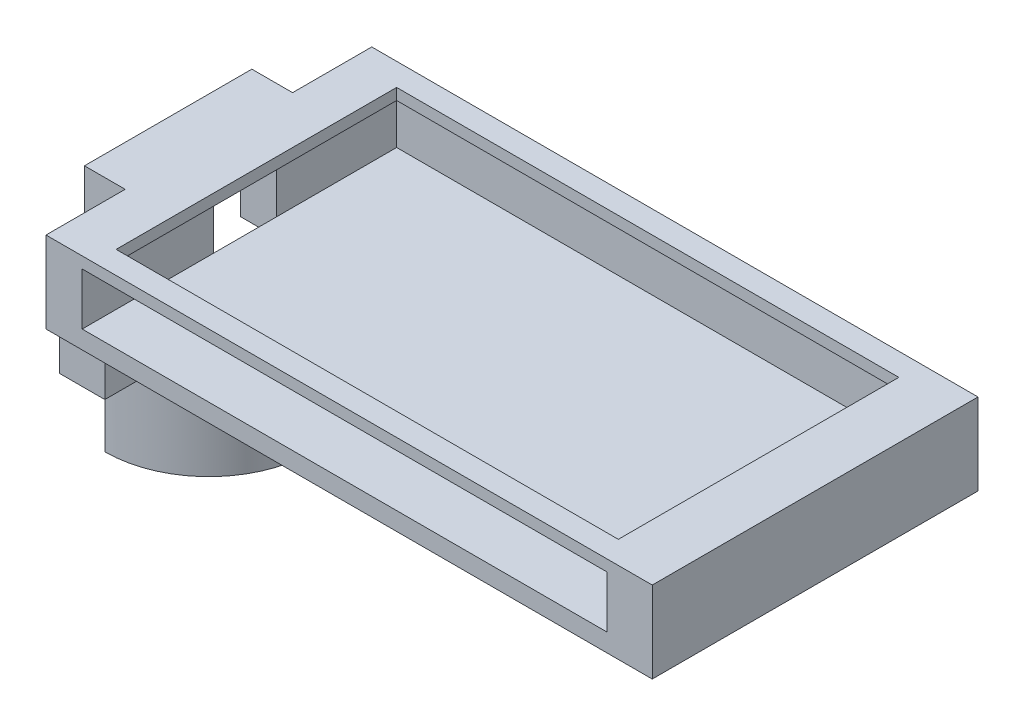
SolidWorks part; units mm, degrees
ref_plane "Front Plane" through (0, 0, 0) normal (0, 0, 1) x (1, 0, 0)
ref_plane "Top Plane" through (0, 0, 0) normal (0, 1, 0) x (1, 0, 0)
ref_plane "Right Plane" through (0, 0, 0) normal (1, 0, 0) x (0, 0, -1)
sketch "Sketch5" plane through (0, 0, 0) normal (0, 1, 0) x (1, 0, 0)
  line L0 (-124, 0) -> (-134, 0)
  line L1 (0, 0) -> (-1.9533, 0)
  line L2 (0, 0) -> (0, 72)
  line L3 (0, 72) -> (-134, 72)
  line L4 (-134, 0) -> (-134, 72)
  line L6 (-10, 2.5) -> (-10, 69.5)
  line L7 (-10, 69.5) -> (-126, 69.5)
  line L8 (-126, 2.5) -> (-126, 69.5)
  line L9 (-126, 2.5) -> (-10, 2.5)
  line L10 (-124, 0) -> (-1.9533, 0)
  dimension "D1" = 72
  dimension "D2" = 134
  dimension "D3" = 116
  dimension "D5" = 10
  dimension "D6" = 2.5
  dimension "D7" = 2.5
extrude "Main Body" add sketch "Sketch5" against normal blind 14 contours L1 L8 L7 L6 L2 L3 L4 region at (-129, 0, -1.5212)
sketch "Sketch6" plane through (0, 0, 0) normal (0, 1, 0) x (1, 0, 0)
  line L5 (-10, 2.5) -> (-126, 2.5)
  line L6 (-10, 2.5) -> (-10, 69.5)
  line L7 (-10, 69.5) -> (-126, 69.5)
  line L8 (-126, 2.5) -> (-126, 69.5)
  line L9 (-12.5, 5) -> (-123.5, 5)
  line L10 (-12.5, 5) -> (-12.5, 67)
  line L11 (-12.5, 67) -> (-123.5, 67)
  line L12 (-123.5, 5) -> (-123.5, 67)
  dimension "D1" = 2.5
  dimension "D2" = 2.5
  dimension "D3" = 2.5
  dimension "D4" = 2.5
extrude "Rail" add sketch "Sketch6" against normal blind 2.5
sketch "Sketch8" plane through (0, 0, 0) normal (0, 0, 1) x (1, 0, 0)
  line L0 (-134, -14) -> (-134, 0) construction
  line L1 (0, -14) -> (-134, -14)
  line L2 (0, -14) -> (0, -18)
  line L3 (0, -18) -> (-134, -18)
  line L4 (-134, -14) -> (-134, -18)
  dimension "D1" = 4
extrude "Cover" add sketch "Sketch8" against normal up to surface (72 mm away) up to face at (-67, -7, -72)
sketch "Sketch9" plane through (-134, 0, 0) normal (-1, 0, 0) x (0, 0, 1)
  line L0 (-72, -18) -> (0, -18) construction
  line L1 (-29, -18) -> (-43, -18)
  line L2 (-29, -18) -> (-29, -4)
  line L3 (-29, -4) -> (-43, -4)
  line L4 (-43, -18) -> (-43, -4)
  line L5 (-72, -18) -> (-72, 0) construction
  dimension "D1" = 14
  dimension "D2" = 14
  dimension "D3" = 29
extrude "SiPM Window" cut sketch "Sketch9" against normal up to surface (8 mm away) up to face at (-126, -8.25, -36)
sketch "Sketch10" plane through (0, -18, 0) normal (0, -1, 0) x (1, 0, 0)
  line L0 (-134, -72) -> (-134, -43) construction
  line L4 (-134, -29) -> (-134, 0) construction
  line L5 (-134, -72) -> (0, -72) construction
  line L6 (-134, -16) -> (-134, -13)
  line L7 (-134, -56) -> (-134, -59)
  arc A0 (-134, -56) -> (-134, -16) centre (-134, -36) ccw
  arc A1 (-134, -59) -> (-134, -13) centre (-134, -36) ccw
  line M4 (-134, -43) -> (-134, -72)
  line M8 (-134, 0) -> (-134, -29)
  dimension "D2" = 20
  dimension "D1" = 36
  dimension "D3" = 3
  dimension "D4" = 3
extrude "Tube Adapter" add sketch "Sketch10" along normal blind 30 contours A1 A0 M4 M8 region at (-133.4857, -18, -14.5)
sketch "Sketch11" plane through (0, -18, 0) normal (0, -1, 0) x (1, 0, 0)
  line L0 (-134, -59) -> (-134, -69)
  line L5 (-134, -72) -> (-134, -59) construction
  line L6 (-134, -69) -> (-124, -69)
  line L7 (-124, -69) -> (-124, -56.7123)
  arc A0 (-134, -59) -> (-124, -56.7123) centre (-134, -36) ccw
  dimension "D1" = 10
  dimension "D2" = 10
extrude "Right Screw Terminal" add sketch "Sketch11" along normal blind 10
sketch "Sketch12" plane through (-134, 0, 0) normal (-1, 0, 0) x (0, 0, 1)
  line L2 (-69, -28) -> (-69, -18) construction
  line L3 (-59, -28) -> (-69, -28) construction
  circle A0 centre (-64, -23) radius 1.524
  dimension "D3" = 5
  dimension "D1" = 3.048
  dimension "D2" = 5
extrude "Right Screw Hole" cut sketch "Sketch12" against normal up to next
sketch "Sketch13" plane through (0, -18, 0) normal (0, -1, 0) x (-1, 0, 0)
  line L2 (134, 13) -> (134, 3)
  line L3 (134, 3) -> (124, 3)
  line L4 (124, 15.2877) -> (124, 3)
  arc A0 (134, 13) -> (124, 15.2877) centre (134, 36) cw
  dimension "D1" = 10
  dimension "D2" = 10
extrude "Left Screw Terminal" add sketch "Sketch13" along normal blind 10
sketch "Sketch14" plane through (-134, 0, 0) normal (-1, 0, 0) x (0, 0, 1)
  line L0 (-3, -28) -> (-3, -18) construction
  line L1 (-3, -28) -> (-13, -28) construction
  circle A0 centre (-8, -23) radius 1.524
  dimension "D3" = 3.048
  dimension "D1" = 5
  dimension "D2" = 5
extrude "Left Screw Hole" cut sketch "Sketch14" against normal up to next
sketch "Sketch15" plane through (-134, 0, 0) normal (-1, 0, 0) x (0, 0, 1)
  line L0 (-29, -18) -> (-16, -18) construction
  line L1 (-17.5, -18) -> (-54.5, -18)
  line L2 (-17.5, -18) -> (-17.5, 0)
  line L3 (-17.5, 0) -> (-54.5, 0)
  line L4 (-54.5, -18) -> (-54.5, 0)
  line L7 (0, 0) -> (-72, 0) construction
  line L8 (-43, -4) -> (-43, -18) construction
  dimension "D1" = 37
  dimension "D2" = 11.5
extrude "SiPM Mount" add sketch "Sketch15" along normal blind 9
sketch "Sketch17" plane through (0, -18, 0) normal (0, -1, 0) x (1, 0, 0)
  line L0 (-126, -29) -> (-134, -29) construction
  line L1 (-134, -19) -> (-141, -19)
  line L2 (-134, -19) -> (-134, -53)
  line L3 (-134, -53) -> (-141, -53)
  line L4 (-141, -19) -> (-141, -53)
  line L5 (-134, -43) -> (-134, -29) construction
  dimension "D1" = 34
  dimension "D2" = 10
  dimension "D3" = 7
extrude "Cut-Extrude1" cut sketch "Sketch17" against normal offset from surface (16 mm away) 2 up to face at (-102.75, 0, -36)
ref_plane "Plane1" through (-144, 0, 0) normal (-1, 0, 0) x (0, 0, 1)
sketch "Sketch18" plane through (-144, 0, 0) normal (-1, 0, 0) x (0, 0, 1)
  line L3 (-56, -48) -> (-56, -18) construction
  line L5 (-56, -48) -> (-16, -48) construction
  circle A0 centre (-36, -40.5) radius 1.524
  dimension "D1" = 3.048
  dimension "D2" = 20
  dimension "D3" = 7.5
extrude "Adapter Hole" cut sketch "Sketch18" against normal up to surface (32.9495 mm away) up to face at (-124.4677, -30.5, -36)
sketch "Sketch19" plane through (0, 0, -2.5) normal (0, 0, -1) x (-1, 0, 0)
  line L0 (126, -14) -> (126, -2.5) construction
  line L1 (10, -14) -> (126, -14)
  line L2 (10, -14) -> (10, -2.5)
  line L3 (10, -2.5) -> (126, -2.5)
  line L4 (126, -14) -> (126, -2.5)
extrude "Cut-Extrude2" cut sketch "Sketch19" against normal blind 10
